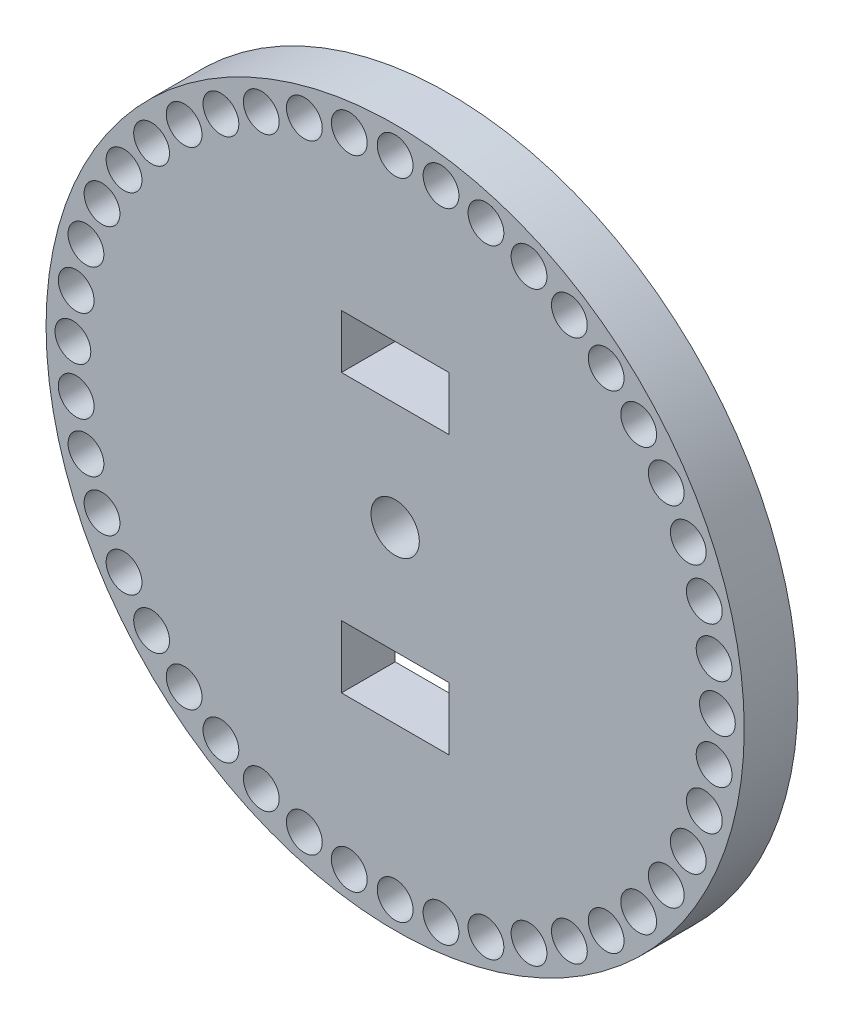
SolidWorks part; units mm, degrees
ref_plane "Front Plane" through (0, 0, 0) normal (0, 0, 1) x (1, 0, 0)
ref_plane "Top Plane" through (0, 0, 0) normal (0, 1, 0) x (1, 0, 0)
ref_plane "Right Plane" through (0, 0, 0) normal (1, 0, 0) x (0, 0, -1)
sketch "Sketch1" plane through (0, 0, 0) normal (0, 0, 1) x (1, 0, 0)
  line L0 (0, 0) -> (0, 9.75) construction
  circle A0 centre (0, 0) radius 19.5
  point P8 (0, 8.25)
  dimension "D1" = 39
extrude "Boss-Extrude1" add sketch "Sketch1" along normal blind 3
sketch "Sketch6" plane through (0, 0, 3) normal (0, 0, 1) x (1, 0, 0)
  line L0 (0, 0) -> (0, 18) construction
  circle A0 centre (0, 18) radius 1
  circle A1 centre (2.5617, 17.8168) radius 1
  circle A2 centre (5.0712, 17.2709) radius 1
  circle A3 centre (7.4775, 16.3734) radius 1
  circle A4 centre (9.7315, 15.1426) radius 1
  circle A5 centre (11.7875, 13.6035) radius 1
  circle A6 centre (13.6035, 11.7875) radius 1
  circle A7 centre (15.1426, 9.7315) radius 1
  circle A8 centre (16.3734, 7.4775) radius 1
  circle A9 centre (17.2709, 5.0712) radius 1
  circle A10 centre (17.8168, 2.5617) radius 1
  circle A11 centre (18, 0) radius 1
  circle A12 centre (17.8168, -2.5617) radius 1
  circle A13 centre (17.2709, -5.0712) radius 1
  circle A14 centre (16.3734, -7.4775) radius 1
  circle A15 centre (15.1426, -9.7315) radius 1
  circle A16 centre (13.6035, -11.7875) radius 1
  circle A17 centre (11.7875, -13.6035) radius 1
  circle A18 centre (9.7315, -15.1426) radius 1
  circle A19 centre (7.4775, -16.3734) radius 1
  circle A20 centre (5.0712, -17.2709) radius 1
  circle A21 centre (2.5617, -17.8168) radius 1
  circle A22 centre (0, -18) radius 1
  circle A23 centre (-2.5617, -17.8168) radius 1
  circle A24 centre (-5.0712, -17.2709) radius 1
  circle A25 centre (-7.4775, -16.3734) radius 1
  circle A26 centre (-9.7315, -15.1426) radius 1
  circle A27 centre (-11.7875, -13.6035) radius 1
  circle A28 centre (-13.6035, -11.7875) radius 1
  circle A29 centre (-15.1426, -9.7315) radius 1
  circle A30 centre (-16.3734, -7.4775) radius 1
  circle A31 centre (-17.2709, -5.0712) radius 1
  circle A32 centre (-17.8168, -2.5617) radius 1
  circle A33 centre (-18, 0) radius 1
  circle A34 centre (-17.8168, 2.5617) radius 1
  circle A35 centre (-17.2709, 5.0712) radius 1
  circle A36 centre (-16.3734, 7.4775) radius 1
  circle A37 centre (-15.1426, 9.7315) radius 1
  circle A38 centre (-13.6035, 11.7875) radius 1
  circle A39 centre (-11.7875, 13.6035) radius 1
  circle A40 centre (-9.7315, 15.1426) radius 1
  circle A41 centre (-7.4775, 16.3734) radius 1
  circle A42 centre (-5.0712, 17.2709) radius 1
  circle A43 centre (-2.5617, 17.8168) radius 1
  dimension "D2" = 2
  dimension "D1" = 18
  dimension "D3" = 44
extrude "Cut-Extrude3" cut sketch "Sketch6" against normal up to surface (3 mm away) up to face at (19.5, 0, 0)
sketch "Sketch7" plane through (0, 0, 3) normal (0, 0, 1) x (1, 0, 0)
  circle A0 centre (0, 0) radius 1.35
  dimension "D1" = 2.7
extrude "Cut-Extrude4" cut sketch "Sketch7" against normal up to surface (3 mm away) up to face at (-16.8168, -2.5617, 0)
sketch "Sketch10" plane through (0, 0, 3) normal (0, 0, 1) x (1, 0, 0)
  line L0 (0, 0) -> (0, 9) construction
  line L1 (3, 9) -> (-3, 9)
  line L2 (-3, 9) -> (-3, 6)
  line L3 (-3, 6) -> (3, 6)
  line L4 (3, 9) -> (3, 6)
  line L5 (0, 0) -> (0, -15.6165) construction
  line L8 (-3, -6) -> (3, -6)
  line L9 (-3, -6) -> (-3, -9.5)
  line L10 (-3, -9.5) -> (3, -9.5)
  line L11 (3, -6) -> (3, -9.5)
  line L12 (-3, -6) -> (3, -9.5) construction
  line L13 (-3, -9.5) -> (3, -6) construction
  point P6 (0, -7.75)
  point P8 (0, 6)
  dimension "D1" = 3
  dimension "D2" = 3
  dimension "D3" = 9
  dimension "D4" = 6
  dimension "D5" = 3.5
  dimension "D6" = 6
extrude "Cut-Extrude5" cut sketch "Sketch10" against normal up to surface (3 mm away) up to face at (1.35, 0, 0)
